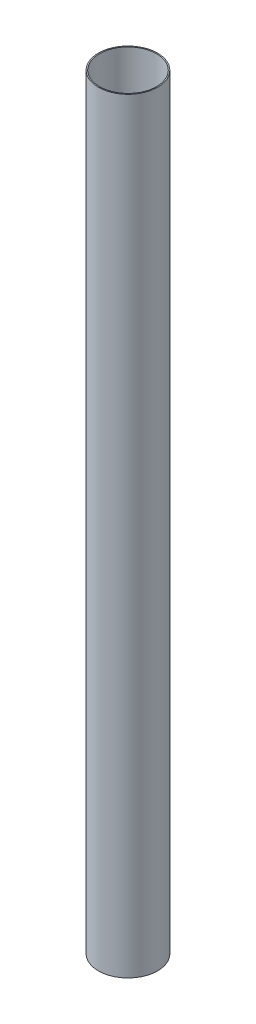
SolidWorks part; units mm, degrees
ref_plane "Front Plane" through (0, 0, 0) normal (0, 0, 1) x (1, 0, 0)
ref_plane "Top Plane" through (0, 0, 0) normal (0, 1, 0) x (1, 0, 0)
ref_plane "Right Plane" through (0, 0, 0) normal (1, 0, 0) x (0, 0, -1)
sketch "Sketch1" plane through (0, 0, 0) normal (0, 1, 0) x (1, 0, 0)
  circle A0 centre (0, 0) radius 41
  circle A1 centre (0, 0) radius 39.5
  dimension "D1" = 82
  dimension "D2" = 79
extrude "Boss-Extrude1" add sketch "Sketch1" along normal blind 1060
